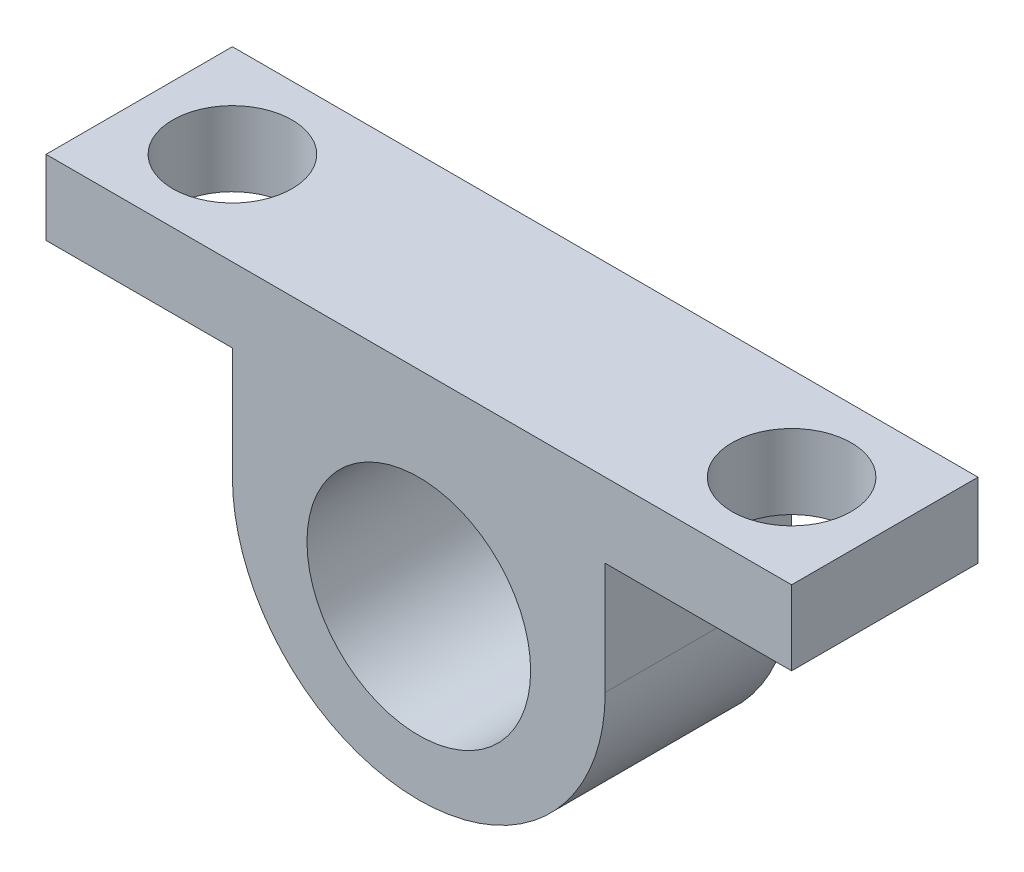
SolidWorks part; units mm, degrees
ref_plane "Front Plane" through (0, 0, 0) normal (0, 0, 1) x (1, 0, 0)
ref_plane "Top Plane" through (0, 0, 0) normal (0, 1, 0) x (1, 0, 0)
ref_plane "Right Plane" through (0, 0, 0) normal (1, 0, 0) x (0, 0, -1)
sketch "Sketch1" plane through (0, 0, 0) normal (0, 1, 0) x (1, 0, 0)
  line L1 (5, -2.5) -> (-5, -2.5)
  line L2 (5, -2.5) -> (5, 2.5)
  line L3 (5, 2.5) -> (-5, 2.5)
  line L4 (-5, -2.5) -> (-5, 2.5)
  line L5 (5, -2.5) -> (-5, 2.5) construction
  line L6 (5, 2.5) -> (-5, -2.5) construction
  point P0 (0, 0)
  dimension "D1" = 5
  dimension "D2" = 10
extrude "Boss-Extrude1" add sketch "Sketch1" against normal blind 10
sketch "Sketch2" plane through (0, 0, -2.5) normal (0, 0, -1) x (-1, 0, 0)
  line L1 (-5, -10) -> (5, -10) construction
  circle A0 centre (0, -5.5) radius 3
  dimension "D1" = 6
  dimension "D2" = 4.5
extrude "Cut-Extrude1" cut sketch "Sketch2" against normal up to next
sketch "Sketch3" plane through (0, 0, 0) normal (0, 1, 0) x (1, 0, 0)
  line L1 (10, 2.5) -> (-10, 2.5)
  line L2 (10, 2.5) -> (10, -2.5)
  line L3 (10, -2.5) -> (-10, -2.5)
  line L4 (-10, 2.5) -> (-10, -2.5)
  line L5 (-5, -2.5) -> (5, -2.5) construction
  line L6 (5, 2.5) -> (-5, 2.5) construction
  line L9 (-5, 2.5) -> (-5, -2.5) construction
  circle A0 centre (-7.5, 0) radius 1.6
  circle A1 centre (7.5, 0) radius 1.6
  point P10 (0, 2.5)
  point P19 (0, 0)
  point P20 (-10, 0)
  dimension "D2" = 3.2
  dimension "D3" = 3.2
  dimension "D1" = 5
  dimension "D4" = 2.5
  dimension "D5" = 2.5
extrude "Boss-Extrude2" add sketch "Sketch3" against normal blind 2
fillet "Fillet1" radius 5 2 edges at (-5, -10, 0) (5, -10, 0)
equation "\"D5@Sketch3\"=\"D4@Sketch3\""
